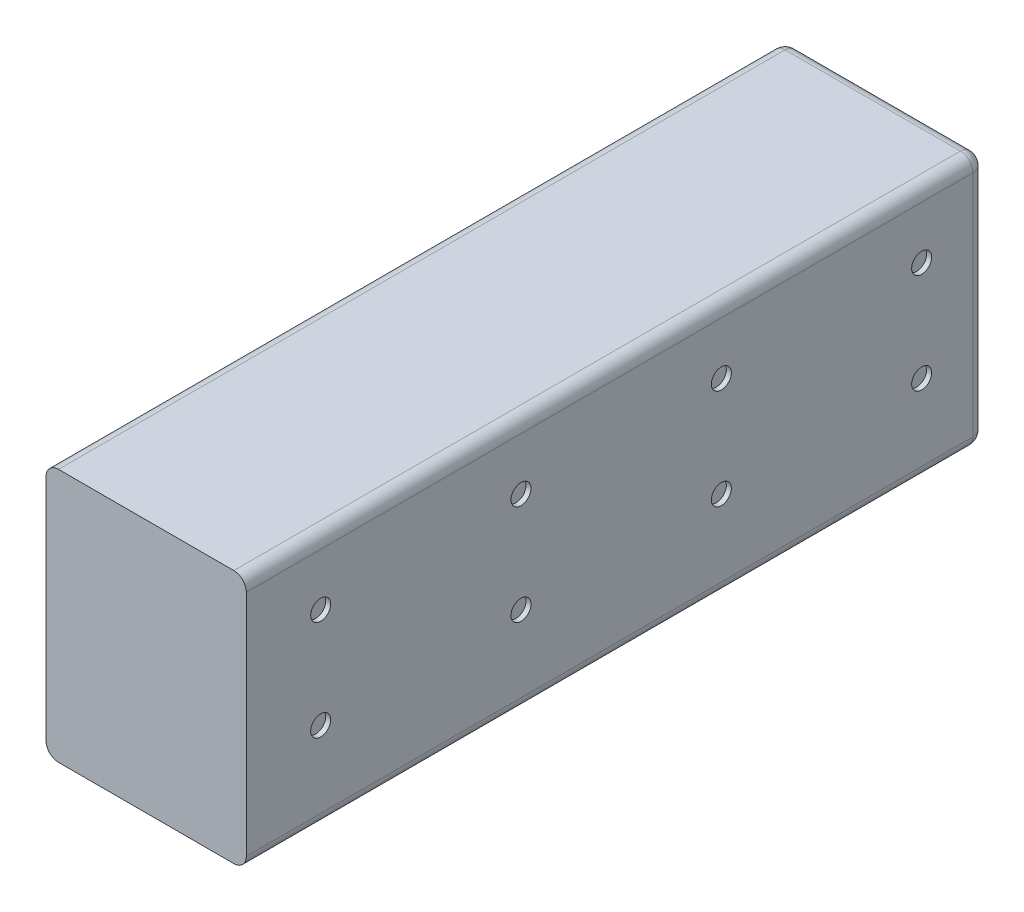
SolidWorks part; units mm, degrees
material "ABS"
ref_plane "Front Plane" through (0, 0, 0) normal (0, 0, 1) x (1, 0, 0)
ref_plane "Top Plane" through (0, 0, 0) normal (0, 1, 0) x (1, 0, 0)
ref_plane "Right Plane" through (0, 0, 0) normal (1, 0, 0) x (0, 0, -1)
sketch "Sketch2" plane through (0, 0, 0) normal (0, 0, 1) x (1, 0, 0)
  line L1 (0, 0) -> (80, 0)
  line L2 (0, 0) -> (0, 101.346)
  line L3 (0, 101.346) -> (80, 101.346)
  line L4 (80, 0) -> (80, 101.346)
extrude "Boss-Extrude1" add sketch "Sketch2" along normal blind 295.148
sketch "Sketch3" plane through (80, 0, 0) normal (1, 0, 0) x (0, 0, -1)
  circle A0 centre (-265.4456, 75.4508) radius 4
  circle A1 centre (-185.4456, 75.4508) radius 4
  circle A2 centre (-105.4456, 75.4508) radius 4
  circle A3 centre (-25.4456, 75.4508) radius 4
  circle A4 centre (-185.4456, 35.4508) radius 4
  circle A5 centre (-105.4456, 35.4508) radius 4
  circle A6 centre (-25.4456, 35.4508) radius 4
  circle A7 centre (-265.4456, 35.4508) radius 4
  dimension "D1" = 4
  dimension "D2" = 2
extrude "Cut-Extrude1" cut sketch "Sketch3" against normal blind 2
ref_plane "Plane1" through (40, 0, 0) normal (-1, 0, 0) x (0, 0, 1)
mirror "Mirror1" about plane through (40, 0, 0) normal (-1, 0, 0) of "Cut-Extrude1"
fillet "Fillet3" radius 5 1 edges at (0, 101.346, 147.574)
fillet "Fillet4" radius 5 1 edges at (80, 101.346, 147.574)
fillet "Fillet5" radius 5 1 edges at (0, 0, 147.574)
fillet "Fillet6" radius 5 1 edges at (80, 0, 147.574)
fillet "Fillet2" radius 5 8 edges at (40, 0, 0) (80, 50.673, 0) (0, 50.673, 0) (40, 101.346, 0) (78.5355, 99.8815, 0) (78.5355, 1.4645, 0) (1.4645, 1.4645, 0) (1.4645, 99.8815, 0)
